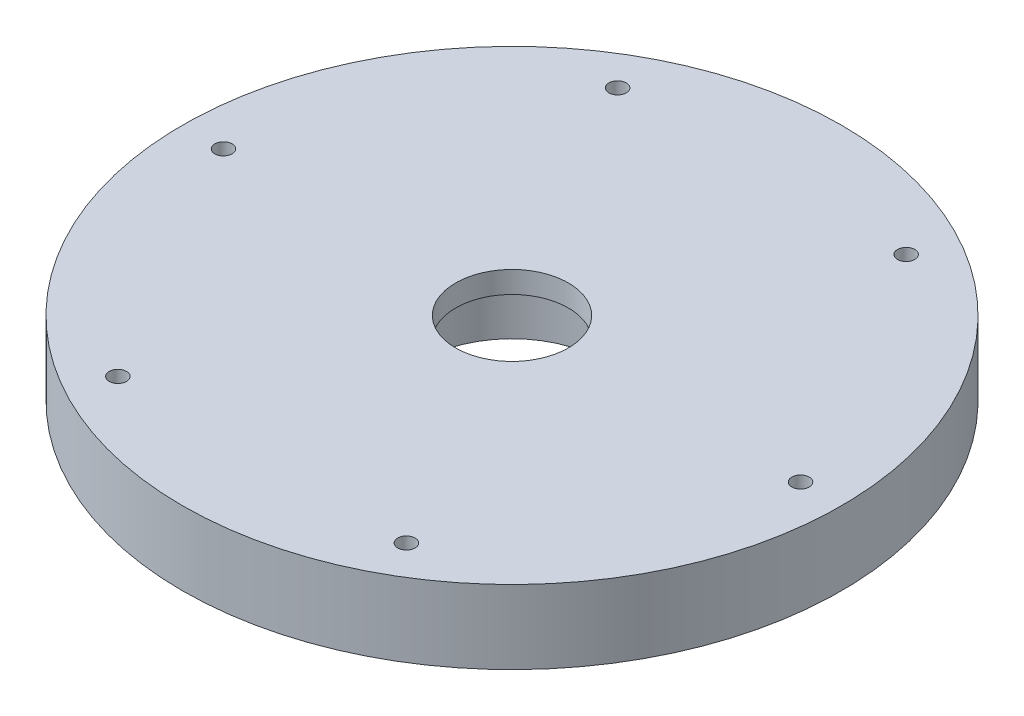
SolidWorks part; units mm, degrees
material "1060 Alloy"
ref_plane "Front Plane" through (0, 0, 0) normal (0, 0, 1) x (1, 0, 0)
ref_plane "Top Plane" through (0, 0, 0) normal (0, 1, 0) x (1, 0, 0)
ref_plane "Right Plane" through (0, 0, 0) normal (1, 0, 0) x (0, 0, -1)
sketch "Sketch1" plane through (0, 0, 0) normal (0, 0, 1) x (1, 0, 0)
  line L0 (0, 38.7087) -> (0, -19.5852) construction
  line L1 (-6.5, 0) -> (-38, 0)
  line L2 (-38, 0) -> (-38, -8.5)
  line L4 (-10.5, -9.75) -> (-10.5, -2.5)
  line L5 (-10.5, -2.5) -> (-6.5, -2.5)
  line L6 (-6.5, -2.5) -> (-6.5, 0)
  line L7 (-10.5, -9.75) -> (-35, -9.75)
  line L8 (-35, -9.75) -> (-35, -8.5)
  line L9 (-35, -8.5) -> (-38, -8.5)
  dimension "D1" = 6.5
  dimension "D2" = 10.5
  dimension "D4" = 38
  dimension "D5" = 3
  dimension "D6" = 1.25
  dimension "D7" = 2.5
  dimension "D3" = 6
revolve "Revolve1" add sketch "Sketch1" angle 360 about L0
sketch "Sketch2" plane through (0, -9.75, 0) normal (0, -1, 0) x (1, 0, 0)
  circle A0 centre (0, 0) radius 33.2687 construction
  circle A1 centre (-33.2687, 0) radius 1
  circle A2 centre (-16.6344, 28.8116) radius 1
  circle A3 centre (16.6344, 28.8116) radius 1
  circle A4 centre (33.2687, 0) radius 1
  circle A5 centre (16.6344, -28.8116) radius 1
  circle A6 centre (-16.6344, -28.8116) radius 1
  point P17 (0, 0)
  dimension "D1" = 2
  dimension "D3" = 66.5375
  dimension "D2" = 6
extrude "Cut-Extrude1" cut sketch "Sketch2" against normal through all
equation "\"Stator_OD\"= 60'No Tolerance given"
equation "\"A\"=35.81 'taken off spec sheet for 06808 (A)"
equation "\"Rotor_ID\"= 30'No Tolerance Given"
equation "\"back_bearing_Thickness\"= 5'-0.12"
equation "\"back_bearing_OD\"= 24'-0.009 https://www.mcmaster.com/5972K155/"
equation "\"Stator_Gap\"= 0.0375'+- 0.0125 (From 1.3.3.1 Kollmorgen manual)"
equation "\"Back_mount_hole\"= 1.75'To be tapped to M2 (USE LOCKTITE)"
equation "\"facePlate_Mount_Hole\"= 2.75'To be tapped to M3"
equation "\"back_bearing_ID\"= 15'"
equation "\"final_shaftD\"= 12'To fit in harmonic"
equation "\"final_shaftL\"= 5.25+3+\"sheet_thick\"+\"connector_thick\"-3+\"harmon_coupleL\"+0.5-\"shaft_Ladjust\"'length to make everything nice and aligned"
equation "\"back_bearing_IDOD\"= 16.5'measured off CAD, actually 16.75, but rounded down to nicer number"
equation "\"rotor_shaftD\"= \"Rotor_ID\" - (\"rotor-shaft_gap\")*2'"
equation "\"front_bearing_ID\"= 12'https://www.mcmaster.com/5972K154/"
equation "\"front_bearing_OD\"= 21'-0.009"
equation "\"front_bearing_IDOD\"= 13.5'Measured off CAD. Actually 13.75, but rounded down"
equation "\"front_bearing_Thickness\"= 5'-0.12"
equation "\"rotor_thickness\"= 2.4'measured off CAD"
equation "\"rotor_height\"= 32.86'+-0.075 taken off spec sheet for 06826 (C)"
equation "\"D1@Sketch1\"=\"final_shaftD\"/2+0.5"
equation "\"D2@Sketch1\"=\"front_bearing_OD\"/2"
equation "\"D4@Sketch1\"=\"Stator_OD\"/2+8"
equation "\"D3@Sketch1\"=\"front_bearing_Thickness\"+1"
equation "\"D3@Sketch2\"=\"Stator_OD\" + \"Stator_Gap\"  + 6.5"
equation "\"D1@Sketch2\"=\"Back_mount_hole\"+0.25"
equation "\"rotor-shaft_gap\" = 0.0185 '+-0.0065 (from manual)"
equation "\"B\"= 26.3'+-0.35 taken off spec sheet for 06826"
equation "\"key_L\"= 20'-0.2 https://www.mcmaster.com/2977N19/"
equation "\"key_H\"= 4'-0.03"
equation "\"key_W\"= 4'-0.03"
equation "\"harmon_keyH\"= 13.8'+0.1 from drawing"
equation "\"harmon_coupleL\"= 21.5' taken from drawing https://www.harmonicdrive.net/_hd/content/caddownloads/dxf/csg-2uh-lw_gearheads/csg-20-100-2uh-lw.pdf"
equation "\"harmon_diam\"= 93' from drawing"
equation "\"harmon_BCD\"= 82' from drawing"
equation "\"harmon_holeD1\"= 5.5' from drawing"
equation "\"harmon_holeD2\"= 5' from drawing"
equation "\"harmon_holeAng\"= 22.5' from drawing"
equation "\"sheet_thick\"= 1/8*25.4 'random, replace w actual sheet thickness when u feel like :)"
equation "\"nut-thickness\"= 5 'idk measure the ones in the shop and adjust"
equation "\"connector_thick\"= 10' random for now"
equation "\"shaft_Ladjust\"= 6.5' sorry. It's silly, but it works."
